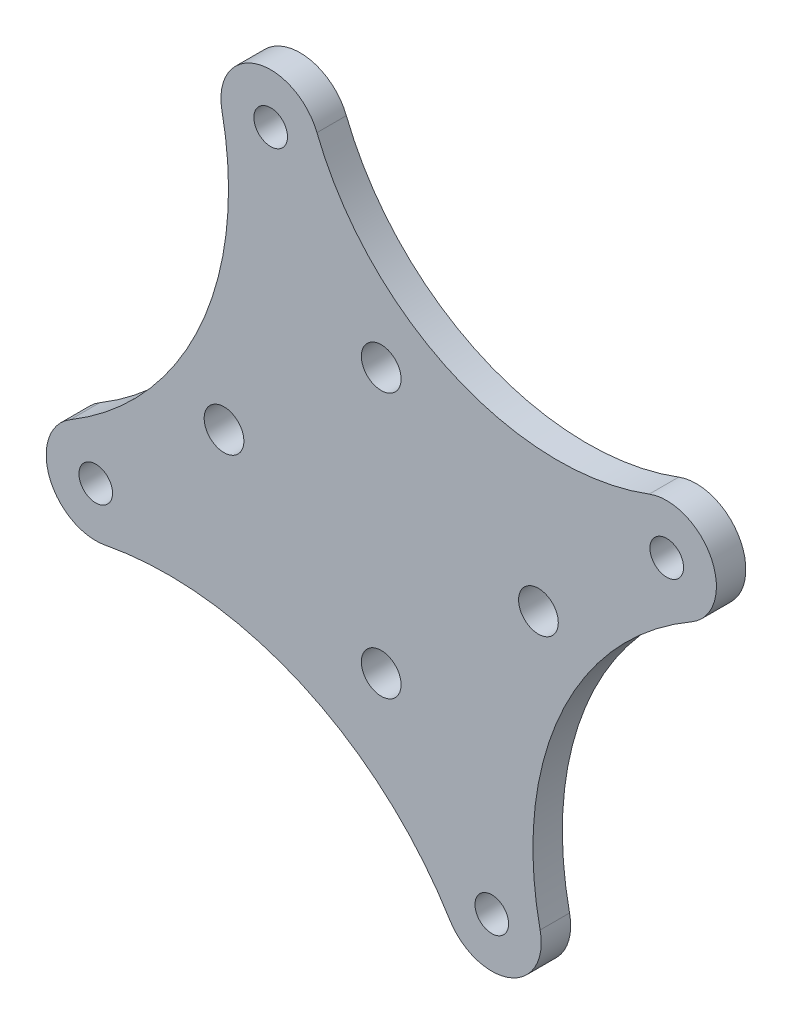
SolidWorks part; units mm, degrees
material "Delrin 2700 NC010, Low Viscosity Acetal Copolymer (SS)"
ref_plane "Front Plane" through (0, 0, 0) normal (0, 0, 1) x (1, 0, 0)
ref_plane "Top Plane" through (0, 0, 0) normal (0, 1, 0) x (1, 0, 0)
ref_plane "Right Plane" through (0, 0, 0) normal (1, 0, 0) x (0, 0, -1)
sketch "Sketch1" plane through (0, 0, 0) normal (0, 0, 1) x (1, 0, 0)
  line L0 (-9.5, 0) -> (9.5, 0) construction
  line L1 (0, 8) -> (0, -8) construction
  line L2 (0, 0) -> (0, 8) construction
  line L3 (0, 0) -> (0, -8) construction
  line L4 (0, 0) -> (-9.5, 0) construction
  line L5 (-9.5, 0) -> (0, 8) construction
  line L6 (-6.6798, 17.2438) -> (6.6831, -17.263) construction
  line L7 (17.2551, 6.6718) -> (-17.2517, -6.6911) construction
  circle A0 centre (0, 8) radius 1.2
  circle A1 centre (-9.5, 0) radius 1.2
  circle A2 centre (9.5, 0) radius 1.2
  circle A3 centre (0, -8) radius 1.2
  circle A4 centre (0, 0) radius 21.5 construction
  circle A5 centre (17.2551, 6.6718) radius 1.016
  circle A6 centre (6.6831, -17.263) radius 1.016
  circle A7 centre (-17.2517, -6.6911) radius 1.016
  circle A8 centre (-6.6798, 17.2438) radius 1.016
  arc A9 (-18.7864, -4.1178) -> (-16.6805, -9.6323) centre (-17.2517, -6.6911) ccw
  arc A10 (4.1316, -18.8189) -> (9.6037, -16.6297) centre (6.6831, -17.263) ccw
  arc A11 (18.7579, 4.0754) -> (16.1975, 9.4792) centre (17.2551, 6.6718) ccw
  arc A12 (-3.8847, 18.3545) -> (-9.6264, 16.6407) centre (-6.6798, 17.2438) ccw
  arc A13 (-16.6805, -9.6323) -> (4.1316, -18.8189) centre (-12.8814, -29.1934) cw
  arc A14 (-18.7864, -4.1178) -> (-9.6264, 16.6407) centre (-28.8238, 12.7116) ccw
  arc A15 (-3.8847, 18.3545) -> (16.1975, 9.4792) centre (10.6745, 24.1401) ccw
  arc A16 (18.7579, 4.0754) -> (9.6037, -16.6297) centre (28.3849, -12.5571) ccw
  point P3 (0, 0)
  point P8 (0, 0)
  point P20 (0.0113, -0.008)
  point P23 (0.0033, -0.0193)
  point P26 (-0.008, -0.0113)
  dimension "D3" = 2.4
  dimension "D4" = 43
  dimension "D6" = 2.032
  dimension "D8" = 2
  dimension "D10" = 2.4
  dimension "D11" = 2
  dimension "D1" = 19
  dimension "D2" = 16
  dimension "D5" = 18.5
  dimension "D9" = 8
  dimension "D12" = 9.5
  dimension "D7" = 4
extrude "Boss-Extrude1" add sketch "Sketch1" along normal blind 1.778
ref_axis "Axis2" through (0, 0, 0) along (0, 0, 1)
